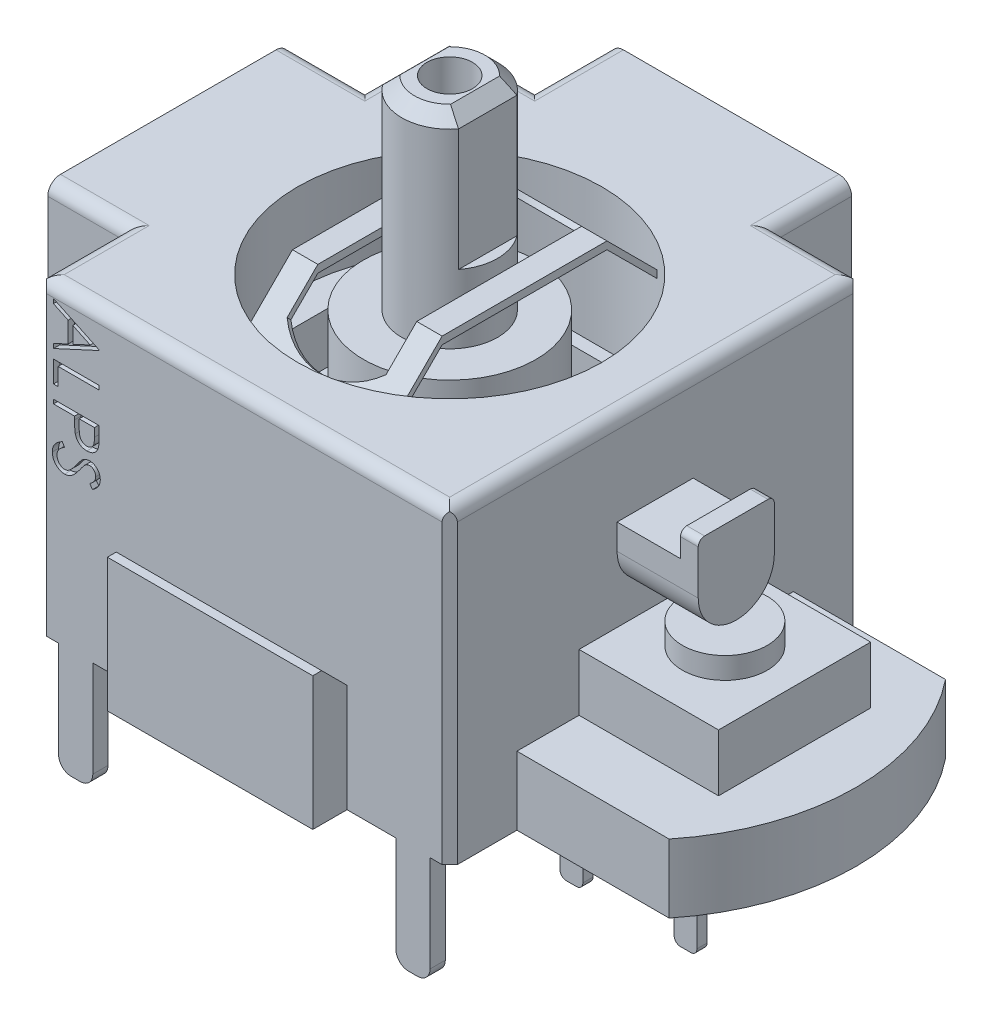
SolidWorks part; units mm, degrees
ref_plane "Front Plane" through (0, 0, 0) normal (0, 0, 1) x (1, 0, 0)
ref_plane "Top Plane" through (0, 0, 0) normal (0, 1, 0) x (1, 0, 0)
ref_plane "Right Plane" through (0, 0, 0) normal (1, 0, 0) x (0, 0, -1)
sketch "Sketch1" plane through (0, 0, 0) normal (0, 1, 0) x (1, 0, 0)
  line L0 (-8.1, 8.1) -> (8.1, -8.1) construction
  line L2 (-8.1, 8.1) -> (8.1, 8.1)
  line L3 (-8.1, 8.1) -> (-8.1, -8.1)
  line L4 (-8.1, -8.1) -> (8.1, -8.1)
  line L5 (8.1, 8.1) -> (8.1, -8.1)
  dimension "D1" = 16.2
  dimension "D2" = 16.2
extrude "Extrude1" add sketch "Sketch1" along normal blind 12.2
sketch "Sketch2" plane through (0, 12.2, 0) normal (0, 1, 0) x (-1, 0, 0)
  circle A0 centre (0, 0) radius 6
  dimension "D1" = 12
extrude "Cut-Extrude1" cut sketch "Sketch2" against normal blind 5.5
sketch "Sketch3" plane through (0, 6.7, 0) normal (0, 1, 0) x (-1, 0, 0)
  line L0 (-4.4721, 4) -> (4.4721, 4)
  line L1 (-4.4721, -4) -> (4.4721, -4)
  line L2 (-4.75, 3.5) -> (4.75, -3.5) construction
  line L3 (-2.75, 3.5) -> (2.75, 3.5)
  line L4 (-4.75, 1.5) -> (-4.75, -1.5)
  line L5 (-2.75, -3.5) -> (2.75, -3.5)
  line L6 (4.75, 1.5) -> (4.75, -1.5)
  circle A0 centre (0, 0) radius 6 construction
  arc A1 (-4.4721, 4) -> (-4.4721, -4) centre (0, 0) ccw
  arc A2 (4.4721, -4) -> (4.4721, 4) centre (0, 0) ccw
  arc A3 (-2.75, 3.5) -> (-4.75, 1.5) centre (-2.75, 1.5) ccw
  arc A4 (-4.75, -1.5) -> (-2.75, -3.5) centre (-2.75, -1.5) ccw
  arc A5 (2.75, -3.5) -> (4.75, -1.5) centre (2.75, -1.5) ccw
  arc A6 (2.75, 3.5) -> (4.75, 1.5) centre (2.75, 1.5) cw
  point P16 (-4.75, -3.5)
  point P22 (4.75, 3.5)
  dimension "D3" = 9.5
  dimension "D5" = 2
  dimension "D1" = 4
  dimension "D2" = 4
  dimension "D4" = 7
extrude "Extrude2" add sketch "Sketch3" along normal blind 2
sketch "Sketch4" plane through (0, 6.7, 0) normal (0, 1, 0) x (-1, 0, 0)
  circle A0 centre (0, 0) radius 3.4
  dimension "D1" = 6.8
extrude "Extrude3" add sketch "Sketch4" along normal blind 4.3
ref_plane "Plane1" through (0, 13.2, 0) normal (0, 1, 0) x (-1, 0, 0)
sketch "Sketch5" plane through (0, 13.2, 0) normal (0, 1, 0) x (-1, 0, 0)
  line L2 (-2.95, -3.25) -> (-1.95, -3.25)
  line L3 (-2.95, -3.25) -> (-2.95, 3.25)
  line L4 (-2.95, 3.25) -> (-1.95, 3.25)
  line L5 (-1.95, -3.25) -> (-1.95, 3.25)
  line L6 (1.95, -3.25) -> (2.95, -3.25)
  line L7 (1.95, -3.25) -> (1.95, 3.25)
  line L8 (1.95, 3.25) -> (2.95, 3.25)
  line L10 (2.95, -3.25) -> (2.95, 3.25)
  line L11 (-8.1, 8.1) -> (-8.1, -8.1) construction
  line L13 (8.1, -8.1) -> (8.1, 8.1) construction
  dimension "D1" = 6.5
  dimension "D2" = 5.15
  dimension "D3" = 5.15
  dimension "D4" = 1
  dimension "D5" = 1
  dimension "D6" = 3.25
extrude "Extrude4" add sketch "Sketch5" against normal blind 0.3
sketch "Sketch14" plane through (0, 11, 0) normal (0, 1, 0) x (-1, 0, 0)
  circle A0 centre (0, 0) radius 1.89
  dimension "D1" = 3.78
extrude "Extrude20" add sketch "Sketch14" along normal blind 8
sketch "Sketch15" plane through (0, 19, 0) normal (0, 1, 0) x (-1, 0, 0)
  line L0 (-1.5, 1.1498) -> (-1.5, -1.1498)
  line L1 (1.5, 1.1498) -> (1.5, -1.1498)
  circle A0 centre (0, 0) radius 1.89 construction
  arc A1 (1.5, -1.1498) -> (1.5, 1.1498) centre (0, 0) ccw
  arc A2 (-1.5, 1.1498) -> (-1.5, -1.1498) centre (0, 0) ccw
  dimension "D2" = 1.5
  dimension "D1" = 1.5
extrude "Cut-Extrude2" cut sketch "Sketch15" against normal blind 5.3
chamfer "Chamfer1" distance 0.5 angle 45 4 edges at (0, 19, -1.89) (1.5, 19, 0) (0, 19, 1.89) (-1.5, 19, 0)
sketch "Sketch16" plane through (0, 19, 0) normal (0, 1, 0) x (-1, 0, 0)
  circle A0 centre (0, 0) radius 0.9
  dimension "D1" = 1.8
extrude "Cut-Extrude3" cut sketch "Sketch16" against normal blind 8.13
combine bodies "Combine1" operation type add bodies to combine 118 104
sketch "Sketch17" plane through (2.95, 0, 0) normal (1, 0, 0) x (0, 0, -1)
  line L0 (-3.25, 13.2) -> (-3.25, 12.9)
  line L1 (-3.25, 12.9) -> (-3.95, 12.2)
  line L2 (-8.1, 12.2) -> (8.1, 12.2) construction
  line L3 (-3.95, 12.2) -> (-4.25, 12.2)
  line L4 (-4.25, 12.2) -> (-3.25, 13.2)
  dimension "D1" = 0.3
extrude "Extrude21" add sketch "Sketch17" against normal up to surface (1 mm away) up to face at (1.95, 13.05, 0)
sketch "Sketch18" plane through (-1.95, 0, 0) normal (1, 0, 0) x (0, 0, -1)
  line L0 (-3.25, 13.2) -> (-3.25, 12.9)
  line L1 (-3.25, 12.9) -> (-3.95, 12.2)
  line L2 (-3.95, 12.2) -> (-4.25, 12.2)
  line L3 (-4.25, 12.2) -> (-3.25, 13.2)
extrude "Extrude22" add sketch "Sketch18" against normal up to surface (1 mm away) up to face at (-2.95, 13.05, 0)
sketch "Sketch19" plane through (2.95, 0, 0) normal (1, 0, 0) x (0, 0, -1)
  line L0 (3.25, 12.9) -> (3.25, 13.2)
  line L1 (3.25, 13.2) -> (4.25, 12.2)
  line L2 (-8.1, 12.2) -> (8.1, 12.2) construction
  line L3 (4.25, 12.2) -> (3.95, 12.2)
  line L4 (3.95, 12.2) -> (3.25, 12.9)
  dimension "D1" = 0.3
extrude "Extrude23" add sketch "Sketch19" against normal up to surface (1 mm away) up to face at (1.95, 12.7667, 1.3667)
sketch "Sketch20" plane through (-1.95, 0, 0) normal (1, 0, 0) x (0, 0, -1)
  line L0 (3.25, 13.2) -> (3.25, 12.9)
  line L1 (3.25, 12.9) -> (3.95, 12.2)
  line L2 (3.95, 12.2) -> (4.25, 12.2)
  line L3 (4.25, 12.2) -> (3.25, 13.2)
extrude "Extrude24" add sketch "Sketch20" against normal up to surface (1 mm away) up to face at (-2.95, 12.7667, 1.3667)
sketch "Sketch22" plane through (0, 8.225, 8.225) normal (0, 0.7071, 0.7071) x (-1, 0, 0)
  line L0 (-1.95, -5.6215) -> (-2.95, -5.6215)
  line L1 (-1.95, -5.6215) -> (-1.95, -0.7253)
  line L2 (-2.95, -5.6215) -> (-2.95, -1.0432)
  line L3 (2.95, -5.6215) -> (1.95, -5.6215)
  line L4 (1.95, -5.6215) -> (1.95, -0.7253)
  line L5 (2.95, -5.6215) -> (2.95, -1.0432)
  ellipse E0 centre (0, -4.7376) end of major axis (-6, -4.7376) minor radius 4.2426 (4.4721, -1.9092) -> (-4.4721, -1.9092) ccw construction
  ellipse E1 centre (0, -4.7376) end of major axis (-6, -4.7376) minor radius 4.2426 (2.95, -1.0432) -> (1.95, -0.7253) ccw
  ellipse E2 centre (0, -4.7376) end of major axis (-6, -4.7376) minor radius 4.2426 (-1.95, -0.7253) -> (-2.95, -1.0432) ccw
extrude "Extrude25" add sketch "Sketch22" against normal blind 0.21
sketch "Sketch23" plane through (1.95, 0, 0) normal (-1, 0, 0) x (0, 0, 1)
  line L0 (3.95, 12.2) -> (4.25, 12.2)
  line L1 (-8.1, 12.2) -> (8.1, 12.2) construction
  line L2 (4.25, 12.2) -> (4.1, 12.05)
  line L3 (4.1, 12.05) -> (3.95, 12.2)
  line L4 (3.95, 12.2) -> (3.25, 12.9) construction
  line L5 (4.1015, 12.0515) -> (4.25, 12.2) construction
extrude "Extrude26" add sketch "Sketch23" against normal up to surface (1 mm away) up to face at (2.95, 11.6013, 4.7002)
sketch "Sketch24" plane through (-2.95, 0, 0) normal (-1, 0, 0) x (0, 0, 1)
  line L0 (4.1015, 12.0515) -> (4.25, 12.2)
  line L1 (-8.1, 12.2) -> (8.1, 12.2) construction
  line L2 (4.25, 12.2) -> (3.953, 12.2)
  line L3 (3.953, 12.2) -> (4.1015, 12.0515)
  line L7 (4.1015, 12.0515) -> (5.2247, 10.9283) construction
  line L8 (4.25, 12.2) -> (5.2247, 11.2253) construction
extrude "Extrude27" add sketch "Sketch24" against normal up to surface (1 mm away) up to face at (-1.95, 12.625, 0)
sketch "Sketch25" plane through (0, 8.225, 8.225) normal (0, 0.7071, 0.7071) x (-1, 0, 0)
  line L0 (-1.95, -7.0357) -> (-1.95, -3.6073) construction
  line L1 (1.95, -7.0357) -> (1.95, -3.6073) construction
  line L2 (-1.95, -5.3215) -> (-1.95, -3.6073)
  line L3 (1.95, -5.3215) -> (1.95, -3.6073)
  arc A0 (-1.95, -3.6073) -> (1.95, -3.6073) centre (0, -7.6196) cw
  arc A1 (-1.95, -5.3215) -> (1.95, -5.3215) centre (0, -7.0196) cw
  ellipse E3 centre (0, -11.6319) end of major axis (0, -20.1172) minor radius 6 (-1.95, -3.6073) -> (-2.95, -4.2431) ccw construction
  dimension "D1" = 0.6
extrude "Extrude28" add sketch "Sketch25" against normal up to surface (0.2121 mm away) up to face at (2.45, 12.475, 3.675)
sketch "Sketch26" plane through (0, 8.225, -8.225) normal (0, 0.7071, -0.7071) x (-1, 0, 0)
  line L0 (1.95, 5.6215) -> (1.95, 0.7253)
  line L1 (1.95, 5.6215) -> (2.95, 5.6215)
  line L2 (2.95, 5.6215) -> (2.95, 1.0432)
  line L3 (-1.95, 5.6215) -> (-2.95, 5.6215)
  line L4 (-2.95, 5.6215) -> (-2.95, 1.0432)
  line L5 (-1.95, 5.6215) -> (-1.95, 0.7253)
  ellipse E0 centre (0, 4.7376) end of major axis (6, 4.7376) minor radius 4.2426 (-4.4721, 1.9092) -> (4.4721, 1.9092) ccw construction
  ellipse E1 centre (0, 4.7376) end of major axis (6, 4.7376) minor radius 4.2426 (-2.95, 1.0432) -> (-1.95, 0.7253) ccw
  ellipse E2 centre (0, 4.7376) end of major axis (6, 4.7376) minor radius 4.2426 (1.95, 0.7253) -> (2.95, 1.0432) ccw
extrude "Extrude30" add sketch "Sketch26" against normal blind 0.21 separate body
sketch "Sketch27" plane through (-2.95, 0, 0) normal (-1, 0, 0) x (0, 0, 1)
  line L0 (-4.1, 12.05) -> (-4.25, 12.2)
  line L1 (-8.1, 12.2) -> (8.1, 12.2) construction
  line L2 (-4.25, 12.2) -> (-3.95, 12.2)
  line L3 (-3.95, 12.2) -> (-4.1, 12.05)
  line L4 (-3.25, 12.9) -> (-3.95, 12.2) construction
  line L5 (-4.1015, 12.0515) -> (-4.25, 12.2) construction
extrude "Extrude31" add sketch "Sketch27" against normal up to surface (1 mm away) up to face at (-1.95, 12.4827, 0.8479)
sketch "Sketch28" plane through (1.95, 0, 0) normal (-1, 0, 0) x (0, 0, 1)
  line L0 (-4.25, 12.2) -> (-4.1, 12.05)
  line L1 (-8.1, 12.2) -> (8.1, 12.2) construction
  line L2 (-4.1, 12.05) -> (-3.95, 12.2)
  line L3 (-3.95, 12.2) -> (-4.25, 12.2)
  line L4 (-3.25, 12.9) -> (-3.95, 12.2) construction
  line L5 (-4.1015, 12.0515) -> (-4.25, 12.2) construction
extrude "Extrude32" add sketch "Sketch28" against normal up to surface (1 mm away) up to face at (2.95, 12.2293, 1.1012)
sketch "Sketch29" plane through (0, 8.225, -8.225) normal (0, 0.7071, -0.7071) x (-1, 0, 0)
  line L0 (-1.95, 3.6073) -> (-1.95, 7.0357) construction
  line L1 (1.95, 3.6073) -> (1.95, 7.0357) construction
  line L2 (1.95, 5.3215) -> (1.95, 3.6073)
  line L3 (-1.95, 5.3215) -> (-1.95, 3.6073)
  arc A0 (1.95, 3.6073) -> (-1.95, 3.6073) centre (0, 14.6612) cw
  arc A1 (1.95, 5.3215) -> (-1.95, 5.3215) centre (0, 15.5112) cw
  dimension "D1" = 0.85
extrude "Extrude34" add sketch "Sketch29" against normal up to surface (0.21 mm away) up to face at (-2.5776, 11.428, -4.725)
sketch "Sketch30" plane through (0, 8.225, -8.225) normal (0, 0.7071, -0.7071) x (-1, 0, 0)
  arc A0 (-1.95, 5.3215) -> (1.95, 5.3215) centre (0, 15.5112) ccw construction
  arc A1 (-1.95, 5.3215) -> (1.95, 5.3215) centre (0, 15.5112) ccw
  arc A2 (-1.95, 5.3215) -> (1.95, 5.3215) centre (0, 7.0261) ccw
  dimension "D1" = 2.59
extrude "Cut-Extrude4" cut sketch "Sketch30" against normal blind 1
sketch "Sketch31" plane through (-8.1, 0, 0) normal (-1, 0, 0) x (0, 0, 1)
  line L0 (-8.1, 12.2) -> (8.1, 12.2) construction
  line L1 (-4.25, 12.2) -> (4.25, 12.2)
  line L2 (-4.75, 11.7) -> (-4.75, 1.55)
  line L3 (-4.25, 1.05) -> (4.25, 1.05)
  line L4 (4.75, 11.7) -> (4.75, 1.55)
  arc A0 (-4.25, 12.2) -> (-4.75, 11.7) centre (-4.25, 11.7) ccw
  arc A1 (4.25, 12.2) -> (4.75, 11.7) centre (4.25, 11.7) cw
  arc A2 (-4.75, 1.55) -> (-4.25, 1.05) centre (-4.25, 1.55) ccw
  arc A3 (4.25, 1.05) -> (4.75, 1.55) centre (4.25, 1.55) ccw
  point P6 (0, 12.2)
  point P11 (-4.75, 12.2)
  dimension "D2" = 0.5
  dimension "D4" = 0.5
  dimension "D1" = 9.5
  dimension "D3" = 11.15
extrude "Extrude35" add sketch "Sketch31" along normal blind 3
sketch "Sketch32" plane through (0, 0, -8.1) normal (0, 0, -1) x (-1, 0, 0)
  line L0 (-8.1, 12.2) -> (8.1, 12.2) construction
  line L1 (-4.25, 12.2) -> (4.25, 12.2)
  line L2 (-4.75, 11.7) -> (-4.75, 1.55)
  line L3 (-4.25, 1.05) -> (4.25, 1.05)
  line L4 (4.75, 11.7) -> (4.75, 1.55)
  line L5 (11.1, 1.05) -> (8.1, 1.05) construction
  arc A0 (-4.25, 12.2) -> (-4.75, 11.7) centre (-4.25, 11.7) ccw
  arc A1 (-4.75, 1.55) -> (-4.25, 1.05) centre (-4.25, 1.55) ccw
  arc A2 (4.25, 1.05) -> (4.75, 1.55) centre (4.25, 1.55) ccw
  arc A3 (4.25, 12.2) -> (4.75, 11.7) centre (4.25, 11.7) cw
  point P8 (0, 12.2)
  point P11 (-4.75, 12.2)
  dimension "D2" = 0.5
  dimension "D1" = 9.5
extrude "Extrude36" add sketch "Sketch32" along normal blind 3
sketch "Sketch33" plane through (0, 0, 8.1) normal (0, 0, 1) x (1, 0, 0)
  line L0 (-8.1, 0) -> (8.1, 0) construction
  line L1 (-4.05, 0) -> (4.05, 0)
  line L2 (-4.05, 0) -> (-4.05, 5.25)
  line L3 (-4.05, 5.25) -> (4.05, 5.25)
  line L4 (4.05, 0) -> (4.05, 5.25)
  line L5 (-8.1, 12.2) -> (8.1, 12.2) construction
  point P8 (0, 0)
  dimension "D1" = 8.1
  dimension "D2" = 6.95
extrude "Extrude37" add sketch "Sketch33" along normal blind 1.35 separate body
chamfer "Chamfer2" distance 1 angle 45 1 edges at (0, 5.25, 8.1)
combine bodies "Combine3" operation type add bodies to combine 139 138
sketch "Sketch34" plane through (0, 0, 0) normal (0, -1, 0) x (1, 0, 0)
  line L0 (8.1, 5.45) -> (8.1, -5.45)
  line L1 (8.1, 8.1) -> (8.1, -8.1) construction
  line L2 (8.1, -5.45) -> (14.1, -5.45)
  line L3 (8.1, 5.45) -> (14.1, 5.45)
  arc A0 (14.1, 5.45) -> (14.1, -5.45) centre (7.35, 0) cw
  point P6 (8.1, 0)
  dimension "D2" = 0.75
  dimension "D3" = 6
  dimension "D1" = 10.9
extrude "Extrude38" add sketch "Sketch34" against normal blind 2.7
sketch "Sketch35" plane through (0, 2.7, 0) normal (0, 1, 0) x (-1, 0, 0)
  line L0 (-8.1, 5.45) -> (-8.1, -5.45) construction
  line L1 (-8.1, -3) -> (-13.6, -3)
  line L2 (-8.1, -3) -> (-8.1, 3)
  line L3 (-8.1, 3) -> (-13.6, 3)
  line L4 (-13.6, -3) -> (-13.6, 3)
  point P6 (-8.1, 0)
  dimension "D1" = 5.5
  dimension "D2" = 6
extrude "Extrude39" add sketch "Sketch35" along normal blind 2.25
sketch "Sketch36" plane through (0, 4.95, 0) normal (0, 1, 0) x (-1, 0, 0)
  line L0 (-13.6, -3) -> (-8.1, -3) construction
  line L1 (-8.1, -3) -> (-8.1, 3) construction
  circle A0 centre (-10.85, 0) radius 1.675
  dimension "D3" = 3.35
  dimension "D1" = 3
  dimension "D2" = 2.75
extrude "Extrude40" add sketch "Sketch36" along normal blind 0.85
sketch "Sketch37" plane through (8.1, 0, 0) normal (1, 0, 0) x (0, 0, -1)
  line L0 (-5.45, 0) -> (5.45, 0) construction
  line L1 (-1.5, 7.55) -> (-1.5, 9.3)
  line L2 (-1.25, 9.55) -> (1.25, 9.55)
  line L3 (1.5, 9.3) -> (1.5, 7.55)
  arc A0 (-1.5, 7.55) -> (1.5, 7.55) centre (0, 7.55) ccw
  arc A1 (-1.5, 9.3) -> (-1.25, 9.55) centre (-1.25, 9.3) cw
  arc A2 (1.25, 9.55) -> (1.5, 9.3) centre (1.25, 9.3) cw
  dimension "D2" = 3
  dimension "D4" = 0.25
  dimension "D1" = 7.55
  dimension "D3" = 2
extrude "Extrude41" add sketch "Sketch37" along normal blind 3.2
sketch "Sketch38" plane through (0, 0, -1.5) normal (0, 0, -1) x (-1, 0, 0)
  line L0 (-8.1, 12.2) -> (-8.1, 0) construction
  line L1 (-8.1, 8.55) -> (-10.6, 8.55)
  line L2 (-8.1, 8.55) -> (-8.1, 9.55)
  line L3 (-8.1, 9.55) -> (-10.6, 9.55)
  line L4 (-10.6, 8.55) -> (-10.6, 9.55)
  line L5 (-11.3, 9.55) -> (-8.1, 9.55) construction
  dimension "D1" = 2.5
  dimension "D2" = 1
extrude "Cut-Extrude5" cut sketch "Sketch38" against normal through all
sketch "Sketch39" plane through (0, 0, -11.1) normal (0, 0, -1) x (-1, 0, 0)
  line L4 (-4.25, 1.05) -> (4.25, 1.05) construction
  circle A0 centre (0, 6.625) radius 1.85
  dimension "D2" = 3.7
  dimension "D1" = 5.575
extrude "Cut-Extrude6" cut sketch "Sketch39" against normal blind 0.25
sketch "Sketch40" plane through (0, 0, -11.1) normal (0, 0, -1) x (-1, 0, 0)
  line L0 (0, 6.7) -> (0, 12.2) construction
  line L1 (-8.1, 0) -> (8.1, 0) construction
  line L2 (0.725, 9.7253) -> (0.725, 10.5816)
  line L3 (-0.725, 9.7253) -> (-0.725, 10.5816)
  line L4 (-3.1003, 7.35) -> (-3.9566, 7.35)
  line L5 (-3.1003, 5.9) -> (-3.9566, 5.9)
  line L6 (-0.725, 3.5247) -> (-0.725, 2.6684)
  line L7 (0.725, 3.5247) -> (0.725, 2.6684)
  line L8 (3.1003, 7.35) -> (3.9566, 7.35)
  line L9 (3.1003, 5.9) -> (3.9566, 5.9)
  arc A0 (-1.0348, 10.8244) -> (-4.1994, 7.6598) centre (0, 6.625) ccw
  arc A1 (-0.9, 9.4868) -> (-2.8618, 7.525) centre (0, 6.625) ccw
  arc A2 (2.8618, 7.525) -> (0.9, 9.4868) centre (0, 6.625) ccw
  arc A3 (4.1994, 7.6598) -> (1.0348, 10.8244) centre (0, 6.625) ccw
  arc A4 (-2.8618, 5.725) -> (-0.9, 3.7632) centre (0, 6.625) ccw
  arc A5 (-4.1994, 5.5902) -> (-1.0348, 2.4256) centre (0, 6.625) ccw
  arc A6 (1.0348, 2.4256) -> (4.1994, 5.5902) centre (0, 6.625) ccw
  arc A7 (0.9, 3.7632) -> (2.8618, 5.725) centre (0, 6.625) ccw
  arc A8 (-0.725, 10.5816) -> (-1.0348, 10.8244) centre (-0.975, 10.5816) ccw
  arc A9 (-0.725, 9.7253) -> (-0.9, 9.4868) centre (-0.975, 9.7253) cw
  arc A10 (-3.1003, 7.35) -> (-2.8618, 7.525) centre (-3.1003, 7.6) ccw
  arc A11 (-3.9566, 7.35) -> (-4.1994, 7.6598) centre (-3.9566, 7.6) cw
  arc A12 (-3.9566, 5.9) -> (-4.1994, 5.5902) centre (-3.9566, 5.65) ccw
  arc A13 (-3.1003, 5.9) -> (-2.8618, 5.725) centre (-3.1003, 5.65) cw
  arc A14 (-0.725, 2.6684) -> (-1.0348, 2.4256) centre (-0.975, 2.6684) cw
  arc A15 (-0.725, 3.5247) -> (-0.9, 3.7632) centre (-0.975, 3.5247) ccw
  arc A16 (0.725, 3.5247) -> (0.9, 3.7632) centre (0.975, 3.5247) cw
  arc A17 (0.725, 2.6684) -> (1.0348, 2.4256) centre (0.975, 2.6684) ccw
  arc A18 (3.1003, 5.9) -> (2.8618, 5.725) centre (3.1003, 5.65) ccw
  arc A19 (3.9566, 5.9) -> (4.1994, 5.5902) centre (3.9566, 5.65) cw
  arc A20 (3.9566, 7.35) -> (4.1994, 7.6598) centre (3.9566, 7.6) ccw
  arc A21 (3.1003, 7.35) -> (2.8618, 7.525) centre (3.1003, 7.6) cw
  arc A22 (0.725, 9.7253) -> (0.9, 9.4868) centre (0.975, 9.7253) ccw
  arc A23 (0.725, 10.5816) -> (1.0348, 10.8244) centre (0.975, 10.5816) cw
  point P26 (-0.725, 9.5361)
  point P33 (-4.2638, 5.9)
  point P36 (-2.9111, 5.9)
  point P39 (-0.725, 2.3612)
  point P42 (-0.725, 3.7139)
  point P45 (0.725, 3.7139)
  point P48 (0.725, 2.3612)
  point P55 (4.2638, 7.35)
  point P58 (2.9111, 7.35)
  point P61 (0.725, 9.5361)
  dimension "D1" = 8.65
  dimension "D2" = 6
  dimension "D9" = 0.25
  dimension "D3" = 6.625
  dimension "D4" = 1.45
  dimension "D5" = 1.45
  dimension "D6" = 1.45
  dimension "D7" = 0.725
  dimension "D8" = 0.725
extrude "Cut-Extrude7" cut sketch "Sketch40" against normal blind 0.25
sketch "Sketch41" plane through (0, 0, 8.1) normal (0, 0, 1) x (1, 0, 0)
  text T0 "<r270>A</r>" font "Century Gothic" height 1.8
  text T1 "<r270>L</r>" font "Century Gothic" height 1.8
  text T2 "<r270>P</r>" font "Century Gothic" height 1.8
  text T3 "<r270>S</r>" font "Century Gothic" height 1.8
extrude "Cut-Extrude8" cut sketch "Sketch41" against normal blind 0.25
sketch "Sketch42" plane through (0, 0, -10.85) normal (0, 0, -1) x (-1, 0, 0)
  line L1 (-0.2, 8.4062) -> (0.2, 8.4062)
  line L2 (-0.5, 8.1062) -> (-0.5, 7.8062)
  line L3 (-0.5, 7.8062) -> (0.5, 7.8062)
  line L4 (0.5, 8.1062) -> (0.5, 7.8062)
  line L5 (-0.2, 4.8438) -> (0.2, 4.8438)
  line L6 (-0.5, 5.1438) -> (-0.5, 5.4438)
  line L7 (-0.5, 5.4438) -> (0.5, 5.4438)
  line L8 (0.5, 5.1438) -> (0.5, 5.4438)
  circle A0 centre (0, 6.625) radius 1.85 construction
  arc A1 (0.2, 8.4062) -> (0.5, 8.1062) centre (0.2, 8.1062) cw
  arc A2 (-0.2, 8.4062) -> (-0.5, 8.1062) centre (-0.2, 8.1062) ccw
  arc A3 (-0.2, 4.8438) -> (-0.5, 5.1438) centre (-0.2, 5.1438) cw
  arc A4 (0.2, 4.8438) -> (0.5, 5.1438) centre (0.2, 5.1438) ccw
  point P10 (0, 8.4062)
  point P13 (0.5, 8.4062)
  point P16 (-0.5, 8.4062)
  point P19 (-0.5, 4.8438)
  point P22 (0.5, 4.8438)
  dimension "D4" = 0.3
  dimension "D1" = 1
  dimension "D2" = 0.6
  dimension "D3" = 0.6
extrude "Extrude42" add sketch "Sketch42" along normal blind 1
chamfer "Chamfer3" distance 0.3 angle 45 10 edges at (0.5, 5.2938, -11.85) (-0.5, 5.2938, -11.85) (0.4121, 4.9317, -11.85) (-0.4121, 4.9317, -11.85) (0, 4.8438, -11.85) (-0.5, 7.9562, -11.85) (0.5, 7.9562, -11.85) (-0.4121, 8.3183, -11.85) (0.4121, 8.3183, -11.85) (0, 8.4062, -11.85)
sketch "Sketch43" plane through (-11.1, 0, 0) normal (-1, 0, 0) x (0, 0, 1)
  line L1 (-4.25, 1.05) -> (4.25, 1.05) construction
  line L2 (-0.725, 10.5816) -> (-0.725, 9.7253)
  line L3 (0.725, 10.5816) -> (0.725, 9.7253)
  line L4 (-3.9566, 7.35) -> (-3.1003, 7.35)
  line L5 (-3.9566, 5.9) -> (-3.1003, 5.9)
  line L6 (-0.725, 3.5247) -> (-0.725, 2.6684)
  line L7 (0.725, 3.5247) -> (0.725, 2.6684)
  line L8 (3.1003, 7.35) -> (3.9566, 7.35)
  line L9 (3.1003, 5.9) -> (3.9566, 5.9)
  circle A0 centre (0, 6.625) radius 1.925
  arc A1 (-4.1994, 5.5902) -> (-1.0348, 2.4256) centre (0, 6.625) ccw
  arc A2 (-2.8618, 5.725) -> (-0.9, 3.7632) centre (0, 6.625) ccw
  arc A3 (2.8618, 7.525) -> (0.9, 9.4868) centre (0, 6.625) ccw
  arc A4 (4.1994, 7.6598) -> (1.0348, 10.8244) centre (0, 6.625) ccw
  arc A5 (-0.9, 9.4868) -> (-2.8618, 7.525) centre (0, 6.625) ccw
  arc A6 (-1.0348, 10.8244) -> (-4.1994, 7.6598) centre (0, 6.625) ccw
  arc A7 (1.0348, 2.4256) -> (4.1994, 5.5902) centre (0, 6.625) ccw
  arc A8 (0.9, 3.7632) -> (2.8618, 5.725) centre (0, 6.625) ccw
  arc A9 (-0.725, 10.5816) -> (-1.0348, 10.8244) centre (-0.975, 10.5816) ccw
  arc A10 (-0.725, 9.7253) -> (-0.9, 9.4868) centre (-0.975, 9.7253) cw
  arc A11 (-3.1003, 7.35) -> (-2.8618, 7.525) centre (-3.1003, 7.6) ccw
  arc A12 (-3.9566, 7.35) -> (-4.1994, 7.6598) centre (-3.9566, 7.6) cw
  arc A13 (-3.9566, 5.9) -> (-4.1994, 5.5902) centre (-3.9566, 5.65) ccw
  arc A14 (-3.1003, 5.9) -> (-2.8618, 5.725) centre (-3.1003, 5.65) cw
  arc A15 (-0.725, 3.5247) -> (-0.9, 3.7632) centre (-0.975, 3.5247) ccw
  arc A16 (-0.725, 2.6684) -> (-1.0348, 2.4256) centre (-0.975, 2.6684) cw
  arc A17 (0.725, 2.6684) -> (1.0348, 2.4256) centre (0.975, 2.6684) ccw
  arc A18 (0.725, 3.5247) -> (0.9, 3.7632) centre (0.975, 3.5247) cw
  arc A19 (3.1003, 5.9) -> (2.8618, 5.725) centre (3.1003, 5.65) ccw
  arc A20 (3.9566, 5.9) -> (4.1994, 5.5902) centre (3.9566, 5.65) cw
  arc A21 (3.9566, 7.35) -> (4.1994, 7.6598) centre (3.9566, 7.6) ccw
  arc A22 (3.1003, 7.35) -> (2.8618, 7.525) centre (3.1003, 7.6) cw
  arc A23 (0.725, 9.7253) -> (0.9, 9.4868) centre (0.975, 9.7253) ccw
  arc A24 (0.725, 10.5816) -> (1.0348, 10.8244) centre (0.975, 10.5816) cw
  point P23 (-0.725, 10.8888)
  point P26 (-0.725, 9.5361)
  point P41 (0.725, 2.3612)
  point P44 (0.725, 3.7139)
  point P51 (4.2638, 7.35)
  point P54 (2.9111, 7.35)
  point P57 (0.725, 9.5361)
  point P60 (0.725, 10.8888)
  dimension "D2" = 3.85
  dimension "D3" = 8.65
  dimension "D4" = 6
  dimension "D10" = 0.25
  dimension "D1" = 5.575
  dimension "D5" = 0.725
  dimension "D6" = 1.45
  dimension "D7" = 1.45
  dimension "D8" = 1.45
  dimension "D9" = 0.725
extrude "Cut-Extrude9" cut sketch "Sketch43" against normal blind 0.25
sketch "Sketch44" plane through (-10.85, 0, 0) normal (-1, 0, 0) x (0, 0, 1)
  line L1 (-0.2, 8.4839) -> (0.2, 8.4839)
  line L2 (-0.5, 8.1839) -> (-0.5, 7.8839)
  line L3 (-0.5, 7.8839) -> (0.5, 7.8839)
  line L4 (0.5, 8.1839) -> (0.5, 7.8839)
  line L5 (-0.2, 4.7661) -> (0.2, 4.7661)
  line L6 (-0.5, 5.0661) -> (-0.5, 5.3661)
  line L7 (-0.5, 5.3661) -> (0.5, 5.3661)
  line L8 (0.5, 5.0661) -> (0.5, 5.3661)
  circle A1 centre (0, 6.625) radius 1.925 construction
  arc A2 (-0.2, 8.4839) -> (-0.5, 8.1839) centre (-0.2, 8.1839) ccw
  arc A3 (0.2, 8.4839) -> (0.5, 8.1839) centre (0.2, 8.1839) cw
  arc A4 (0.2, 4.7661) -> (0.5, 5.0661) centre (0.2, 5.0661) ccw
  arc A5 (-0.2, 4.7661) -> (-0.5, 5.0661) centre (-0.2, 5.0661) cw
  point P10 (0, 4.7661)
  point P13 (-0.5, 8.4839)
  point P20 (-0.5, 4.7661)
  dimension "D3" = 0.6
  dimension "D5" = 0.3
  dimension "D1" = 1
  dimension "D2" = 1
  dimension "D4" = 0.6
extrude "Extrude43" add sketch "Sketch44" along normal blind 1
chamfer "Chamfer4" distance 0.3 angle 45 10 edges at (-11.85, 5.2161, -0.5) (-11.85, 5.2161, 0.5) (-11.85, 4.8539, -0.4121) (-11.85, 4.8539, 0.4121) (-11.85, 4.7661, 0) (-11.85, 8.0339, 0.5) (-11.85, 8.0339, -0.5) (-11.85, 8.3961, 0.4121) (-11.85, 8.3961, -0.4121) (-11.85, 8.4839, 0)
sketch "Sketch45" plane through (0, 0, 0) normal (0, -1, 0) x (1, 0, 0)
  line L0 (8.1, -8.1) -> (-8.1, -8.1) construction
  line L1 (-7.325, -8.1) -> (-5.975, -8.1)
  line L2 (-7.325, -8.1) -> (-7.325, -7.5)
  line L3 (-7.325, -7.5) -> (-5.975, -7.5)
  line L4 (-5.975, -8.1) -> (-5.975, -7.5)
  line L6 (5.975, -8.1) -> (7.325, -8.1)
  line L7 (5.975, -8.1) -> (5.975, -7.5)
  line L8 (5.975, -7.5) -> (7.325, -7.5)
  line L9 (7.325, -8.1) -> (7.325, -7.5)
  line L10 (4.05, 8.1) -> (8.1, 8.1) construction
  line L11 (-7.325, 7.5) -> (-5.975, 7.5)
  line L12 (-7.325, 7.5) -> (-7.325, 8.1)
  line L13 (-7.325, 8.1) -> (-5.975, 8.1)
  line L14 (-5.975, 7.5) -> (-5.975, 8.1)
  line L15 (5.975, 7.5) -> (7.325, 7.5)
  line L16 (5.975, 7.5) -> (5.975, 8.1)
  line L17 (5.975, 8.1) -> (7.325, 8.1)
  line L20 (7.325, 7.5) -> (7.325, 8.1)
  line L22 (-8.1, 8.1) -> (-4.05, 8.1) construction
  point P22 (-6.65, 7.5)
  point P23 (6.65, 7.5)
  dimension "D1" = 0.6
  dimension "D2" = 0.6
  dimension "D3" = 1.35
  dimension "D4" = 1.35
  dimension "D5" = 6.65
  dimension "D6" = 6.65
  dimension "D7" = 0.6
  dimension "D8" = 0.6
extrude "Extrude44" add sketch "Sketch45" along normal blind 4.3
fillet "Fillet1" radius 0.5 8 edges at (-5.975, -4.3, 7.8) (-7.325, -4.3, 7.8) (7.325, -4.3, 7.8) (5.975, -4.3, 7.8) (7.325, -4.3, -7.8) (5.975, -4.3, -7.8) (-7.325, -4.3, -7.8) (-5.975, -4.3, -7.8)
sketch "Sketch46" plane through (0, 1.05, 0) normal (0, -1, 0) x (1, 0, 0)
  line L1 (3, -9.55) -> (2, -9.55)
  line L2 (3, -9.55) -> (3, -10.05)
  line L3 (3, -10.05) -> (2, -10.05)
  line L4 (2, -9.55) -> (2, -10.05)
  line L5 (0.5, -9.55) -> (-0.5, -9.55)
  line L6 (0.5, -9.55) -> (0.5, -10.05)
  line L7 (0.5, -10.05) -> (-0.5, -10.05)
  line L8 (-0.5, -9.55) -> (-0.5, -10.05)
  line L9 (-2, -9.55) -> (-3, -9.55)
  line L10 (-2, -9.55) -> (-2, -10.05)
  line L11 (-2, -10.05) -> (-3, -10.05)
  line L12 (-3, -9.55) -> (-3, -10.05)
  point P12 (-0.5, -9.8)
  point P13 (0, -9.55)
  point P14 (2.5, -10.05)
  point P15 (-2.5, -10.05)
  dimension "D1" = 1
  dimension "D2" = 0.5
  dimension "D3" = 0.5
  dimension "D4" = 0.5
  dimension "D5" = 9.8
  dimension "D6" = 5
  dimension "D7" = 1.5
extrude "Extrude45" add sketch "Sketch46" along normal blind 3.5
sketch "Sketch47" plane through (0, 1.05, 0) normal (0, -1, 0) x (1, 0, 0)
  line L1 (-10.05, -3) -> (-9.55, -3)
  line L2 (-10.05, -3) -> (-10.05, -2)
  line L3 (-10.05, -2) -> (-9.55, -2)
  line L4 (-9.55, -3) -> (-9.55, -2)
  line L5 (-10.05, -0.5) -> (-9.55, -0.5)
  line L6 (-10.05, -0.5) -> (-10.05, 0.5)
  line L7 (-10.05, 0.5) -> (-9.55, 0.5)
  line L8 (-9.55, -0.5) -> (-9.55, 0.5)
  line L9 (-10.05, 2) -> (-9.55, 2)
  line L10 (-10.05, 2) -> (-10.05, 3)
  line L11 (-10.05, 3) -> (-9.55, 3)
  line L12 (-9.55, 2) -> (-9.55, 3)
  point P12 (-9.8, 0.5)
  point P13 (-9.55, 0)
  point P14 (-10.05, 2.5)
  point P15 (-10.05, -2.5)
  dimension "D1" = 0.5
  dimension "D2" = 1
  dimension "D3" = 9.8
  dimension "D4" = 5
  dimension "D5" = 1.5
extrude "Extrude46" add sketch "Sketch47" along normal blind 3.5
fillet "Fillet2" radius 0.5 12 edges at (3, -2.45, -9.8) (2, -2.45, -9.8) (0.5, -2.45, -9.8) (-0.5, -2.45, -9.8) (-2, -2.45, -9.8) (-3, -2.45, -9.8) (-9.8, -2.45, -3) (-9.8, -2.45, -2) (-9.8, -2.45, -0.5) (-9.8, -2.45, 0.5) (-9.8, -2.45, 3) (-9.8, -2.45, 2)
sketch "Sketch48" plane through (0, 0, 0) normal (0, -1, 0) x (1, 0, 0)
  line L1 (7.8, 3.45) -> (8.7, 3.45)
  line L2 (7.8, 3.45) -> (7.8, 3.05)
  line L3 (7.8, 3.05) -> (8.7, 3.05)
  line L4 (8.7, 3.45) -> (8.7, 3.05)
  line L5 (12.3, 3.45) -> (13.2, 3.45)
  line L6 (12.3, 3.45) -> (12.3, 3.05)
  line L7 (12.3, 3.05) -> (13.2, 3.05)
  line L8 (13.2, 3.45) -> (13.2, 3.05)
  line L9 (7.8, -3.45) -> (8.7, -3.45)
  line L10 (7.8, -3.45) -> (7.8, -3.05)
  line L11 (7.8, -3.05) -> (8.7, -3.05)
  line L12 (8.7, -3.45) -> (8.7, -3.05)
  line L13 (12.3, -3.45) -> (13.2, -3.45)
  line L14 (12.3, -3.45) -> (12.3, -3.05)
  line L15 (12.3, -3.05) -> (13.2, -3.05)
  line L16 (13.2, -3.45) -> (13.2, -3.05)
  point P16 (8.25, 3.05)
  point P17 (8.25, 3.45)
  point P18 (12.75, 3.45)
  point P19 (13.2, -3.25)
  point P20 (13.2, 3.25)
  point P21 (7.8, 3.25)
  dimension "D1" = 0.4
  dimension "D2" = 0.9
  dimension "D3" = 8.25
  dimension "D4" = 4.5
  dimension "D5" = 6.5
  dimension "D6" = 3.25
extrude "Extrude47" add sketch "Sketch48" along normal blind 2.75
fillet "Fillet3" radius 0.25 8 edges at (13.2, -2.75, -3.25) (12.3, -2.75, -3.25) (8.7, -2.75, -3.25) (7.8, -2.75, -3.25) (13.2, -2.75, 3.25) (12.3, -2.75, 3.25) (8.7, -2.75, 3.25) (7.8, -2.75, 3.25)
chamfer "Chamfer5" distance 0.3 angle 45 4 edges at (-8.1, 6.1, -8.1) (8.1, 6.1, -8.1) (8.1, 6.1, 8.1) (-8.1, 6.1, 8.1)
fillet "Fillet4" radius 0.5 6 edges at (8.1, 12.2, 0) (0, 12.2, 8.1)
